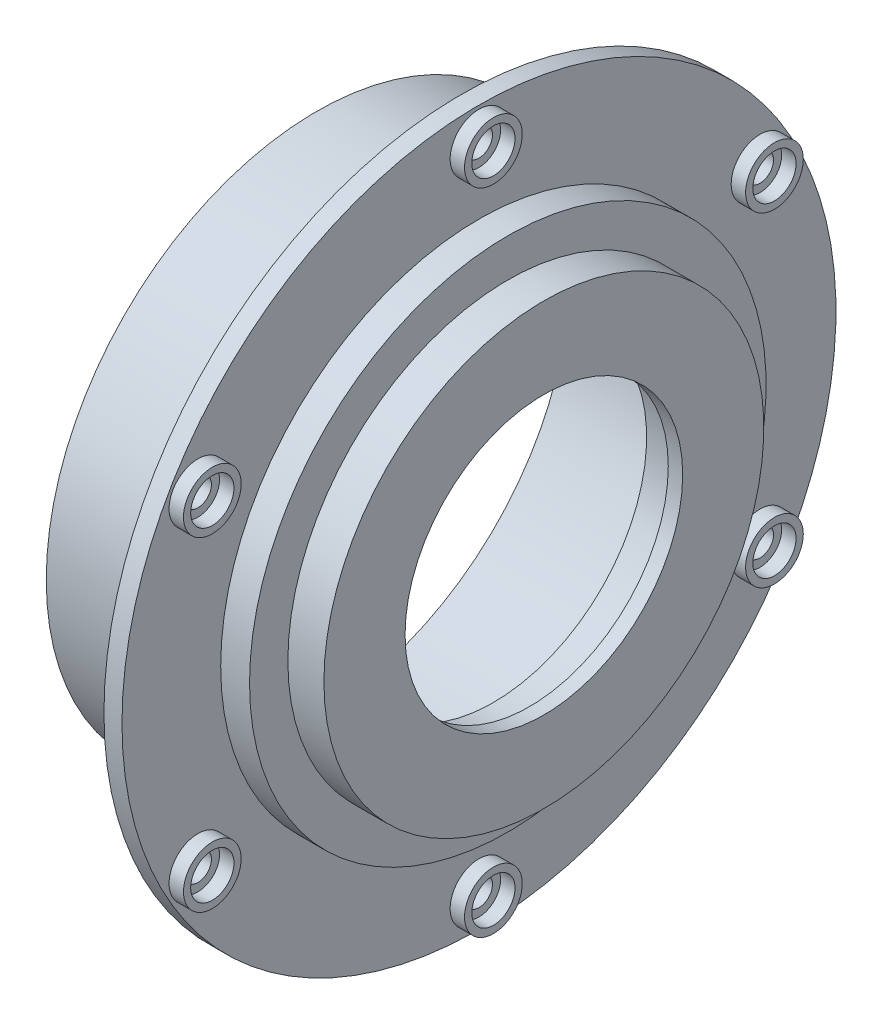
SolidWorks part; units mm, degrees
ref_plane "Front Plane" through (0, 0, 0) normal (0, 0, 1) x (1, 0, 0)
ref_plane "Top Plane" through (0, 0, 0) normal (0, 1, 0) x (1, 0, 0)
ref_plane "Right Plane" through (0, 0, 0) normal (1, 0, 0) x (0, 0, -1)
sketch "Sketch1" plane through (0, 0, 0) normal (0, 0, 1) x (1, 0, 0)
  line L0 (0, 5) -> (0, -70) construction
  line L1 (0, 0) -> (39, 0)
  line L2 (0, 0) -> (0, 5)
  line L3 (0, 5) -> (40, 5)
  line L5 (0, -70) -> (55.5444, -70) construction
  line L6 (39, 0) -> (39, -9)
  line L9 (40, 5) -> (40, 29)
  line L10 (40, 29) -> (45, 29)
  line L11 (39, -9) -> (49, -9)
  line L13 (49, -9) -> (49, -27.5)
  line L14 (49, -27.5) -> (59, -27.5)
  line L15 (59, -27.5) -> (59, -31.5)
  line L16 (59, -31.5) -> (63, -31.5)
  line L17 (63, -31.5) -> (63, -9)
  line L18 (63, -9) -> (53, -9)
  line L19 (53, -9) -> (53, 1.6237)
  line L20 (53, 1.6237) -> (45, 1.6237)
  line L21 (45, 29) -> (45, 1.6237)
revolve "Revolve1" add sketch "Sketch1" angle 360 about L5
sketch "Sketch3" plane through (45, 0, 0) normal (1, 0, 0) x (0, 0, -1)
  line L0 (0, -70) -> (0, 29) construction
  line L1 (0, 29) -> (0, 20) construction
  circle A0 centre (0, -70) radius 99 construction
  circle A1 centre (0, 20) radius 3.75
  circle A2 centre (77.9423, -25) radius 3.75
  circle A3 centre (77.9423, -115) radius 3.75
  circle A4 centre (0, -160) radius 3.75
  circle A5 centre (-77.9423, -115) radius 3.75
  circle A6 centre (-77.9423, -25) radius 3.75
  point P21 (0, -70)
  dimension "D1" = 7.5
  dimension "D2" = 6
extrude "Cut-Extrude1" cut sketch "Sketch3" against normal blind 10
sketch "Sketch4" plane through (45, 0, 0) normal (1, 0, 0) x (0, 0, -1)
  circle A1 centre (0, 20) radius 6
  circle A2 centre (77.9423, -25) radius 6
  circle A4 centre (77.9423, -115) radius 6
  circle A6 centre (0, -160) radius 6
  circle A8 centre (-77.9423, -115) radius 6
  circle A10 centre (-77.9423, -25) radius 6
  circle A13 centre (0, 20) radius 8
  circle A14 centre (77.9423, -25) radius 8
  circle A15 centre (77.9423, -115) radius 8
  circle A16 centre (0, -160) radius 8
  circle A17 centre (-77.9423, -115) radius 8
  circle A18 centre (-77.9423, -25) radius 8
  point P22 (0, -70)
  point P28 (0, -70)
  dimension "D1" = 12
  dimension "D3" = 16
  dimension "D2" = 6
  dimension "D4" = 6
extrude "Boss-Extrude1" add sketch "Sketch4" along normal blind 4
